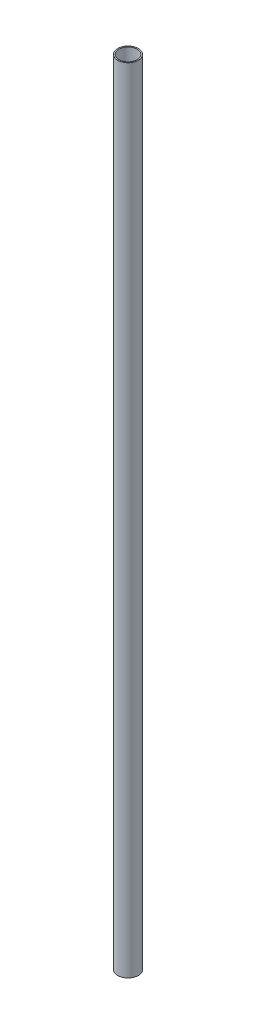
SolidWorks part; units mm, degrees
material "Zoltek Panex 33"
ref_plane "Front Plane" through (0, 0, 0) normal (0, 0, 1) x (1, 0, 0)
ref_plane "Top Plane" through (0, 0, 0) normal (0, 1, 0) x (1, 0, 0)
ref_plane "Right Plane" through (0, 0, 0) normal (1, 0, 0) x (0, 0, -1)
sketch "Sketch1" plane through (0, 0, 0) normal (0, 1, 0) x (1, 0, 0)
  circle A0 centre (0, 0) radius 13
  circle A1 centre (0, 0) radius 11.5
  dimension "D1" = 26
  dimension "D2" = 23
extrude "Boss-Extrude1" add sketch "Sketch1" along normal blind 1000
